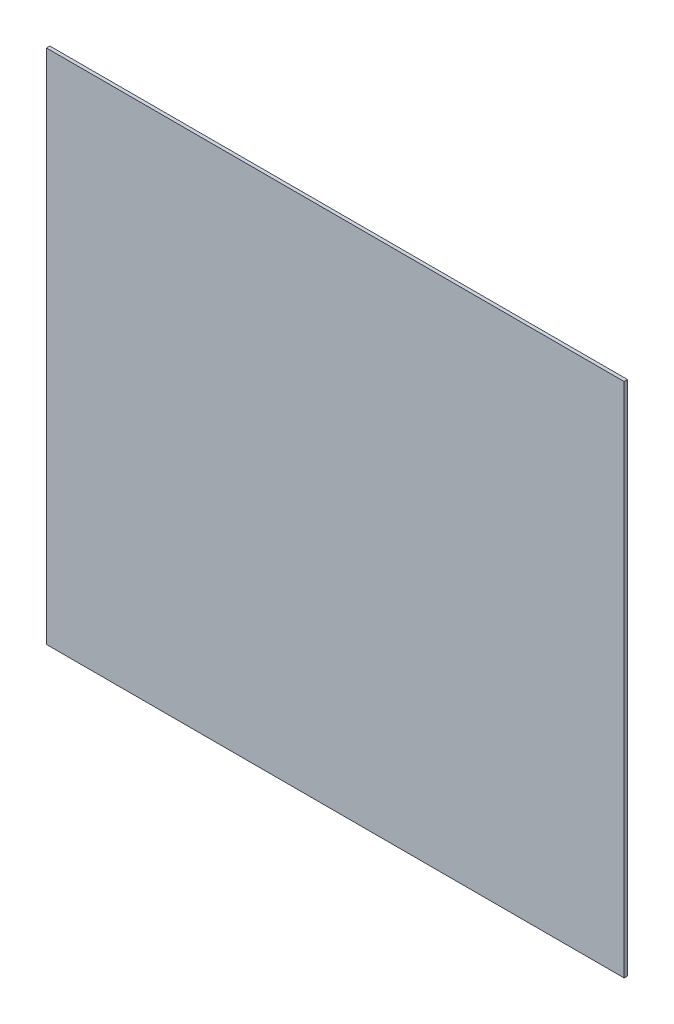
SolidWorks part; units mm, degrees
ref_plane "Front Plane" through (0, 0, 0) normal (0, 0, 1) x (1, 0, 0)
ref_plane "Top Plane" through (0, 0, 0) normal (0, 1, 0) x (1, 0, 0)
ref_plane "Right Plane" through (0, 0, 0) normal (1, 0, 0) x (0, 0, -1)
sketch "Sketch1" plane through (0, 0, 0) normal (0, 0, 1) x (1, 0, 0)
  line L1 (170, 152) -> (-170, 152)
  line L2 (170, 152) -> (170, -152)
  line L3 (170, -152) -> (-170, -152)
  line L4 (-170, 152) -> (-170, -152)
  line L5 (170, 152) -> (-170, -152) construction
  line L6 (170, -152) -> (-170, 152) construction
  line L7 (120, -128) -> (-128, -128)
  line L8 (127, -121) -> (127, 108)
  line L9 (120, 115) -> (-128, 115)
  line L10 (-135, -121) -> (-135, 108)
  line L11 (131, -117) -> (-131, 117) construction
  line L12 (131, 117) -> (-131, -117) construction
  line L13 (-170, 152) -> (-225, 152)
  line L14 (-170, 152) -> (-170, -152)
  line L15 (-170, -152) -> (-225, -152)
  line L16 (-225, 152) -> (-225, -152)
  line L17 (-197.5, -152) -> (-197.5, 152) construction
  line L18 (-170, 0) -> (-225, 0) construction
  arc A0 (-128, -128) -> (-135, -121) centre (-128, -121) cw
  arc A1 (120, -128) -> (127, -121) centre (120, -121) ccw
  arc A2 (127, 108) -> (120, 115) centre (120, 108) ccw
  arc A3 (-128, 115) -> (-135, 108) centre (-128, 108) ccw
  point P0 (0, 0)
  point P5 (0, 0)
  point P134 (-197.5, 0)
  dimension "D5" = 7
  dimension "D1" = 340
  dimension "D2" = 304
  dimension "D3" = 37
  dimension "D4" = 43
  dimension "D6" = 55
  dimension "D7" = 24
  dimension "D8" = 262
extrude "Boss-Extrude1" [suppressed] add sketch "Sketch1" along normal blind 2 contours L1 L4 L3 L2 A3 L9 A2 L8 A1 L7 A0 L10 | L13 L16 L15 L4
extrude "Boss-Extrude2" add sketch "Sketch1<3>" along normal blind 2 contours L1 L4 L3 L2 A3 L9 A2 L8 A1 L7 A0 L10 | L9 A3 L10 A0 L7 A1 L8 A2 region at (165.4391, 0, 0) region at (-4, -6.5, 0)
sketch "Sketch1<3>" plane through (0, 0, 0) normal (0, 0, 1) x (1, 0, 0) same geometry as "Sketch1"
